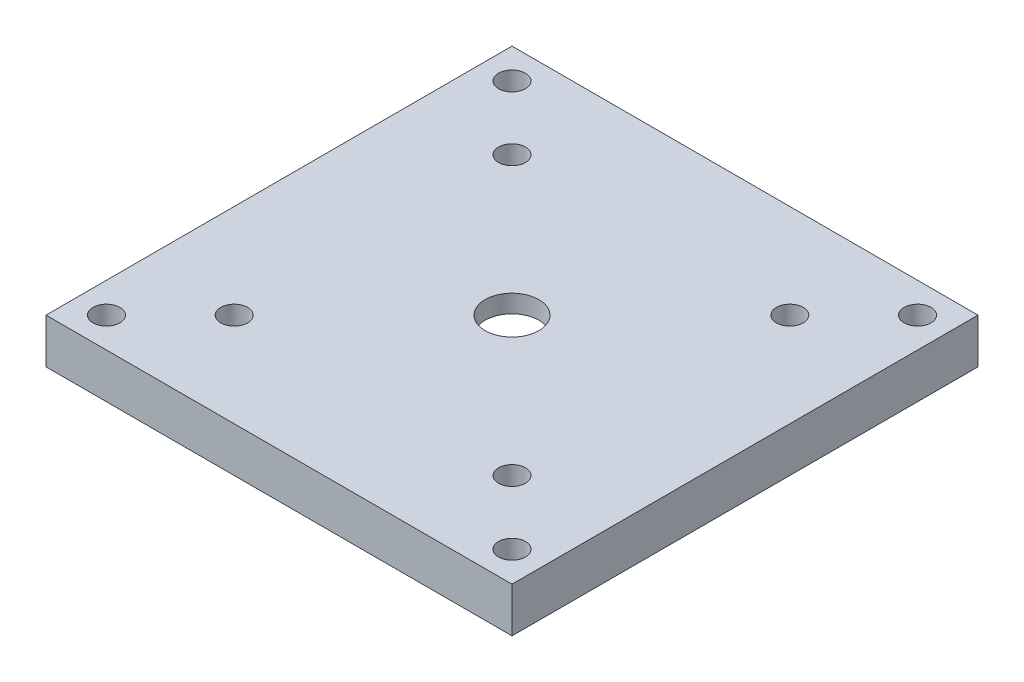
SolidWorks part; units mm, degrees
ref_plane "Front Plane" through (0, 0, 0) normal (0, 0, 1) x (1, 0, 0)
ref_plane "Top Plane" through (0, 0, 0) normal (0, 1, 0) x (1, 0, 0)
ref_plane "Right Plane" through (0, 0, 0) normal (1, 0, 0) x (0, 0, -1)
sketch "Sketch1" plane through (0, 0, 0) normal (0, 1, 0) x (1, 0, 0)
  line L0 (0, 26) -> (0, -26) construction
  line L1 (26, 26) -> (-26, 26)
  line L2 (26, 26) -> (26, -26)
  line L3 (26, -26) -> (-26, -26)
  line L4 (-26, 26) -> (-26, -26)
  line L5 (26, 26) -> (-26, -26) construction
  line L6 (26, -26) -> (-26, 26) construction
  line L7 (-26, 0) -> (26, 0) construction
  line L9 (15.5, -15.5) -> (-15.5, -15.5) construction
  line L10 (15.5, -15.5) -> (15.5, 15.5) construction
  line L11 (15.5, 15.5) -> (-15.5, 15.5) construction
  line L12 (-15.5, -15.5) -> (-15.5, 15.5) construction
  line L13 (15.5, -15.5) -> (-15.5, 15.5) construction
  line L14 (15.5, 15.5) -> (-15.5, -15.5) construction
  circle A4 centre (22.6274, 22.6274) radius 1.5
  circle A5 centre (22.6274, -22.6274) radius 1.5
  circle A6 centre (-22.6274, 22.6274) radius 1.5
  circle A7 centre (-22.6274, -22.6274) radius 1.5
  circle A8 centre (0, 0) radius 10
  circle A9 centre (0, 0) radius 3
  circle A10 centre (15.5, 15.5) radius 1.5
  circle A11 centre (15.5, -15.5) radius 1.5
  circle A12 centre (-15.5, -15.5) radius 1.5
  circle A13 centre (-15.5, 15.5) radius 1.5
  point P0 (0, 0)
  point P18 (0, 0)
  dimension "D3" = 3
  dimension "D6" = 3
  dimension "D8" = 20
  dimension "D9" = 6
  dimension "D1" = 52
  dimension "D2" = 52
  dimension "D4" = 31
  dimension "D7" = 32
extrude "Boss-Extrude1" add sketch "Sketch1" along normal blind 5 contours L1 L4 L3 L2
extrude "Cut-Extrude2" cut sketch "Sketch1<5>" along normal blind 13 contours A11 | A13 | A7 | A6 | A4 | A5
sketch "Sketch1<5>" plane through (0, 0, 0) normal (0, 1, 0) x (1, 0, 0) same geometry as "Sketch1"
extrude "Cut-Extrude5" cut sketch "Sketch1<8>" along normal blind 3 contours A8
sketch "Sketch1<8>" plane through (0, 0, 0) normal (0, 1, 0) x (1, 0, 0) same geometry as "Sketch1"
extrude "Cut-Extrude6" cut sketch "Sketch1<9>" along normal blind 24 contours A9
sketch "Sketch1<9>" plane through (0, 0, 0) normal (0, 1, 0) x (1, 0, 0) same geometry as "Sketch1"
extrude "Cut-Extrude7" cut sketch "Sketch1<10>" along normal blind 24 contours A10 | A12
sketch "Sketch1<10>" plane through (0, 0, 0) normal (0, 1, 0) x (1, 0, 0) same geometry as "Sketch1"
